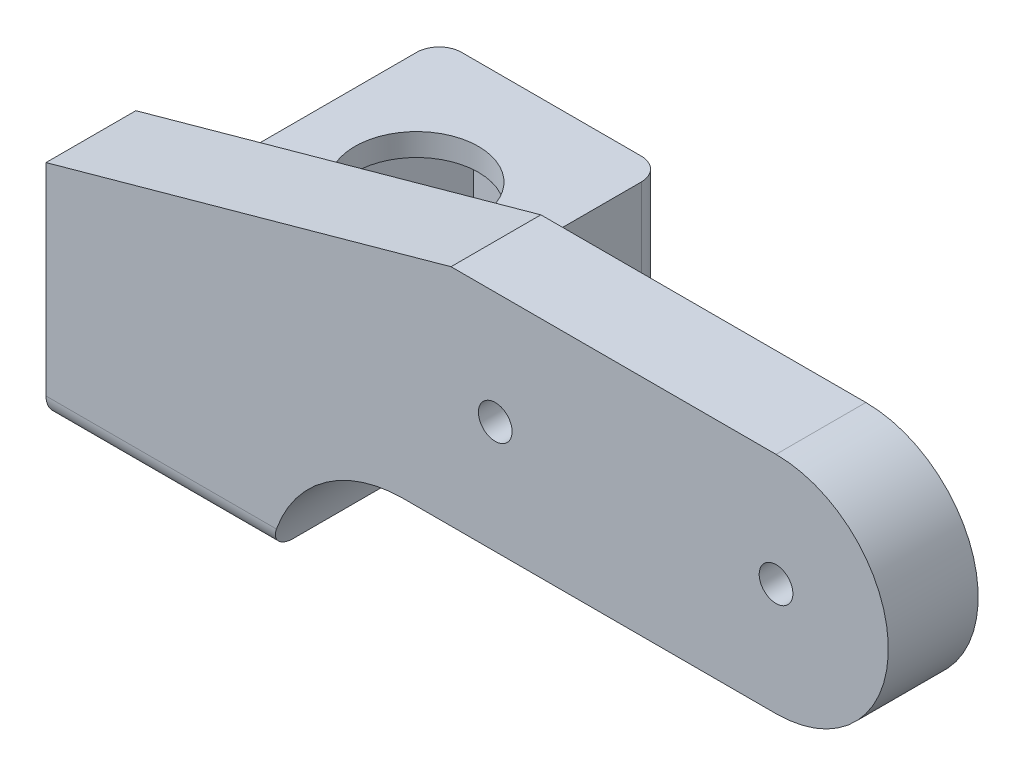
SolidWorks part; units mm, degrees
ref_plane "Front Plane" through (0, 0, 0) normal (0, 0, 1) x (1, 0, 0)
ref_plane "Top Plane" through (0, 0, 0) normal (0, 1, 0) x (1, 0, 0)
ref_plane "Right Plane" through (0, 0, 0) normal (1, 0, 0) x (0, 0, -1)
sketch "Sketch1" plane through (0, 0, 0) normal (0, 0, 1) x (1, 0, 0)
  line L1 (-25, 10) -> (40, 10)
  line L2 (-25, 10) -> (-25, -10)
  line L3 (-25, -10) -> (40, -10)
  arc A0 (40, -10) -> (40, 10) centre (40, 0) ccw
  dimension "D5" = 20
  dimension "D1" = 20
  dimension "D2" = 10
  dimension "D3" = 65
  dimension "D4" = 25
extrude "Boss-Extrude1" add sketch "Sketch1" along normal blind 8
sketch "Sketch2" plane through (0, 0, 8) normal (0, 0, 1) x (1, 0, 0)
  line L0 (40, 10) -> (-25, 10) construction
  circle A1 centre (40, 0) radius 1.5
  dimension "D2" = 3
  dimension "D1" = 10
  dimension "D3" = 40
extrude "Cut-Extrude1" cut sketch "Sketch2" against normal blind 10
sketch "Sketch3" plane through (0, 0, 0) normal (0, 0, -1) x (-1, 0, 0)
  line L0 (-40, 10) -> (25, 10) construction
  circle A1 centre (-15, 0) radius 1.5
  dimension "D2" = 3
  dimension "D1" = 10
  dimension "D3" = 15
extrude "Cut-Extrude2" cut sketch "Sketch3" against normal blind 10
sketch "Sketch6" plane through (0, 0, 0) normal (0, 0, -1) x (-1, 0, 0)
  line L1 (25, -10) -> (5, -10)
  line L2 (25, -10) -> (25, -20)
  line L3 (25, -20) -> (5, -20)
  line L4 (5, -10) -> (5, -20)
  dimension "D1" = 20
  dimension "D2" = 10
extrude "Boss-Extrude3" add sketch "Sketch6" along normal blind 30 and the other way blind 8
fillet "Fillet3" radius 12 1 edges at (-5, -10, 4)
sketch "Sketch7" plane through (0, -10, 0) normal (0, 1, 0) x (1, 0, 0)
  line L1 (-5, 30) -> (-25, 30)
  line L2 (-5, 30) -> (-5, 0)
  line L3 (-5, 0) -> (-25, 0)
  line L4 (-25, 30) -> (-25, 0)
extrude "Boss-Extrude4" add sketch "Sketch7" along normal blind 2
sketch "Sketch8" plane through (0, -20, 0) normal (0, -1, 0) x (1, 0, 0)
  line L1 (-5, 8) -> (-25, 8) construction
  line L2 (-5, 0) -> (-5, -30) construction
  line L4 (-12.0928, -7.0126) -> (-20.4637, -8.4886)
  line L15 (-20.4637, -8.4886) -> (-23.3709, -16.476)
  line L16 (-23.3709, -16.476) -> (-17.9072, -22.9874)
  line L17 (-17.9072, -22.9874) -> (-9.5363, -21.5114)
  line L18 (-9.5363, -21.5114) -> (-6.6291, -13.524)
  line L19 (-6.6291, -13.524) -> (-12.0928, -7.0126)
  dimension "D2" = 8.5
  dimension "D3" = 1.6291
  dimension "D1" = 15.0126
extrude "Cut-Extrude3" cut sketch "Sketch8" against normal blind 10
sketch "Sketch9" plane through (0, -10, 0) normal (0, -1, 0) x (1, 0, 0)
  line L0 (-20.4637, -8.4886) -> (-9.5363, -21.5114) construction
  line L1 (-12.0928, -7.0126) -> (-17.9072, -22.9874) construction
  line L2 (16.927, -11) -> (16.927, -10.0428) construction
  circle A0 centre (-15, -15) radius 5.5
  dimension "D1" = 11
extrude "Cut-Extrude4" cut sketch "Sketch9" against normal blind 10
fillet "Fillet4" radius 5 2 edges at (-5, -14, 0) (-15, -8, 0)
fillet "Fillet5" radius 2 4 edges at (-15, -20, 8) (-25, 10, 4) (-5, -14, -30) (-25, -14, -30)
sketch "Sketch10" plane through (0, 0, 8) normal (0, 0, 1) x (1, 0, 0)
  line L0 (-25, 0) -> (11.062, 10)
  line L1 (-25, 8) -> (-25, -18) construction
  line L2 (40, 10) -> (-23, 10) construction
  line L7 (-25, 8) -> (-25, -18)
  line L8 (-25, -18) -> (-4.4815, -18)
  line L9 (6.8322, -10) -> (40, -10)
  line L10 (40, 10) -> (-23, 10)
  line L11 (-25, 8) -> (-25, 0)
  line L14 (11.062, 10) -> (-23, 10)
  arc A3 (6.8322, -10) -> (-4.4815, -18) centre (6.8322, -22) ccw
  arc A4 (40, -10) -> (40, 10) centre (40, 0) ccw
  arc A5 (-23, 10) -> (-25, 8) centre (-23, 8) ccw
  arc A8 (-23, 10) -> (-25, 8) centre (-23, 8) ccw
  dimension "D1" = 0
extrude "Cut-Extrude5" cut sketch "Sketch10" against normal blind 10
sketch "Sketch11" plane through (0, -20, 0) normal (0, -1, 0) x (1, 0, 0)
  line L0 (-25, 6) -> (-25, -28) construction
  line L1 (-25, -27) -> (-5, -27)
  line L2 (-25, -27) -> (-25, -30)
  line L3 (-25, -30) -> (-5, -30)
  line L4 (-5, -27) -> (-5, -30)
  line L5 (-7, -30) -> (-23, -30) construction
  line L6 (-5, -5) -> (-5, -28) construction
  dimension "D1" = 3
extrude "Cut-Extrude6" cut sketch "Sketch11" against normal blind 15
fillet "Fillet6" radius 2 2 edges at (-5, -14, -27) (-25, -14, -27)
